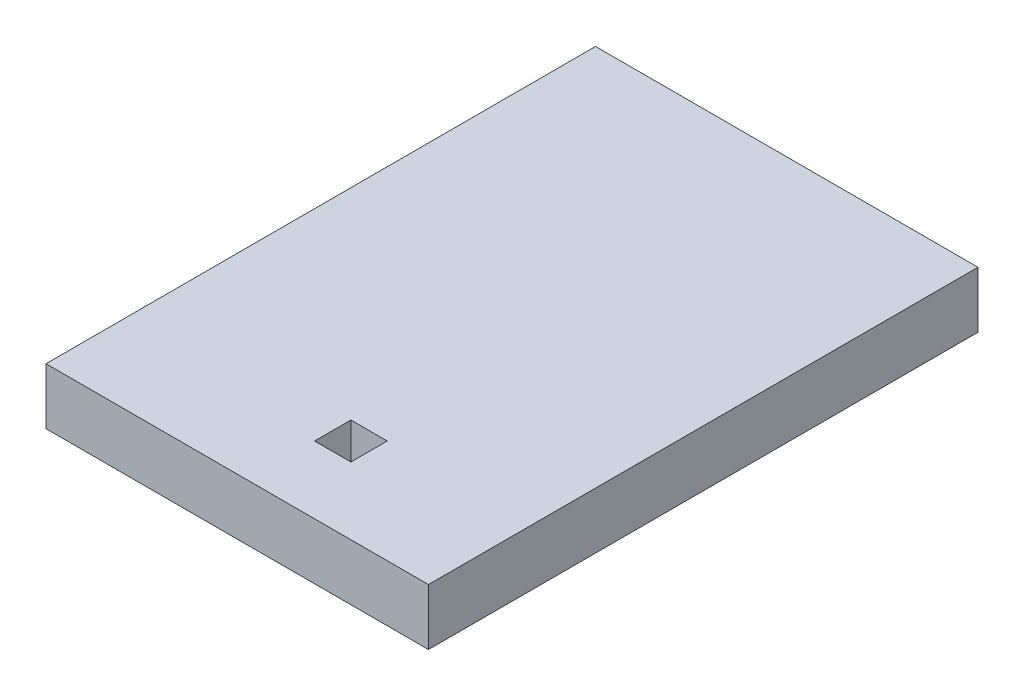
SolidWorks part; units mm, degrees
ref_plane "Front Plane" through (0, 0, 0) normal (0, 0, 1) x (1, 0, 0)
ref_plane "Top Plane" through (0, 0, 0) normal (0, 1, 0) x (1, 0, 0)
ref_plane "Right Plane" through (0, 0, 0) normal (1, 0, 0) x (0, 0, -1)
sketch "Sketch1" plane through (0, 0, 0) normal (0, 1, 0) x (1, 0, 0)
  line L0 (0, 15.5) -> (0, 0) construction
  line L1 (-9.2, 15.5) -> (9.2, 15.5)
  line L2 (-9.2, 15.5) -> (-9.2, -15.5)
  line L3 (-9.2, -15.5) -> (9.2, -15.5)
  line L4 (9.2, 15.5) -> (9.2, -15.5)
  line L5 (0, -9.65) -> (0, 0) construction
  line L6 (-1.025, -9.65) -> (1.025, -9.65)
  line L7 (-1.025, -9.65) -> (-1.025, -11.7)
  line L8 (-1.025, -11.7) -> (1.025, -11.7)
  line L9 (1.025, -9.65) -> (1.025, -11.7)
  line L11 (-9.2, 15.5) -> (-12.375, 15.5)
  line L12 (-9.2, 15.5) -> (-9.2, -15.5)
  line L13 (-9.2, -15.5) -> (-12.375, -15.5)
  line L14 (-12.375, 15.5) -> (-12.375, -15.5)
  point P11 (1.025, -10.675)
  point P14 (9.2, 0)
  dimension "D1" = 18.4
  dimension "D2" = 31
  dimension "D3" = 26.175
  dimension "D4" = 2.05
  dimension "D5" = 3.175
extrude "Boss-Extrude1" add sketch "Sketch1" along normal blind 3.175 contours L4 L1 L2 L3 L6 L9 L8 L7 | L11 L14 L13 L2 region at (0, 0, -0.0792) region at (-10.7875, 0, 0)
